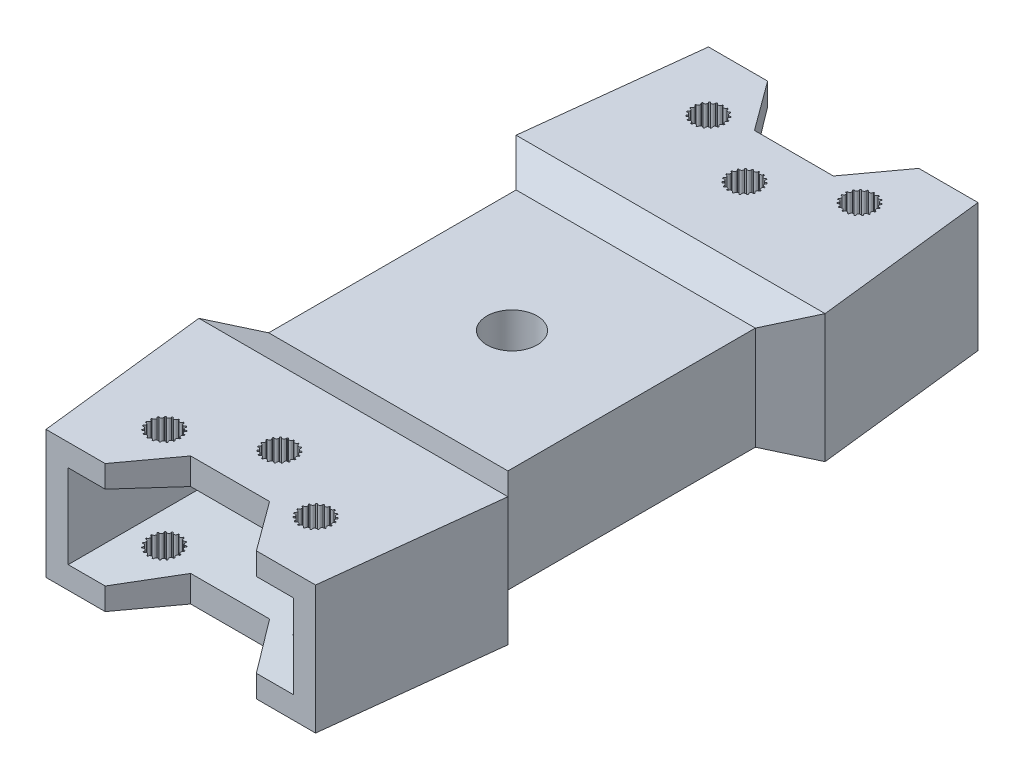
SolidWorks part; units mm, degrees
material "ABS"
ref_plane "Front Plane" through (0, 0, 0) normal (0, 0, 1) x (1, 0, 0)
ref_plane "Top Plane" through (0, 0, 0) normal (0, 1, 0) x (1, 0, 0)
ref_plane "Right Plane" through (0, 0, 0) normal (1, 0, 0) x (0, 0, -1)
sketch "Sketch2" plane through (0, 0, 0) normal (0, 1, 0) x (1, 0, 0)
  line L0 (0, 0) -> (0, 3) construction
  line L1 (0, 175) -> (168.3275, 175) construction
  line L2 (168.3275, 175) -> (-205.8504, 175) construction
  line L3 (-15, 350) -> (-35, 175)
  line L4 (-35, 175) -> (-15, 0)
  line L5 (15, 350) -> (35, 175)
  line L6 (35, 175) -> (15, 0)
  line L7 (0, 335) -> (0, 350) construction
  line L8 (31.3255, 207.1517) -> (24.2545, 200.0806)
  line L9 (24.2545, 200.0806) -> (24.2545, 149.9194)
  line L10 (31.3255, 142.8483) -> (24.2545, 149.9194)
  line L11 (-31.3255, 142.8483) -> (-24.2545, 149.9194)
  line L12 (-24.2545, 200.0806) -> (-24.2545, 149.9194)
  line L13 (-31.3255, 207.1517) -> (-24.2545, 200.0806)
  circle A0 centre (0, 350) radius 3
  circle A1 centre (0, 0) radius 3
  arc A2 (15, 350) -> (-15, 350) centre (0, 350) ccw
  arc A3 (-15, 0) -> (15, 0) centre (0, 0) ccw
  circle A4 centre (0, 175) radius 5.1
  point P21 (24.2545, 175)
  dimension "D2" = 6
  dimension "D3" = 6
  dimension "D4" = 30
  dimension "D5" = 30
  dimension "D7" = 10.2
  dimension "D1" = 350
  dimension "D6" = 35
  dimension "D8" = 32.1517
  dimension "D9" = 10
extrude "Boss-Extrude1" add sketch "Sketch2" along normal blind 26 contours L4 A3 L6 L10 L9 L8 L5 A2 L3 L13 L12 L11 A4 A0 A1 region at (0, 0, -361.1487)
sketch "Sketch3" plane through (0, 0, 0) normal (1, 0, 0) x (0, 0, -1)
  line L0 (-15, 13) -> (370.2756, 13) construction
  line L1 (-15, 26) -> (-15, 0) construction
  line L3 (177.6378, 13) -> (177.6378, -89.1144) construction
  line L5 (-50, 21) -> (20, 21)
  line L6 (-50, 21) -> (-50, 5)
  line L7 (-50, 5) -> (20, 5)
  line L8 (20, 21) -> (20, 5)
  line L9 (-50, 21) -> (20, 5) construction
  line L10 (-50, 5) -> (20, 21) construction
  dimension "D1" = 16
  dimension "D2" = 35
extrude "Cut-Extrude1" cut sketch "Sketch3" against normal mid plane 55
sketch "Sketch4" plane through (0, 26, 0) normal (0, 1, 0) x (1, 0, 0)
  circle A0 centre (0, 175) radius 5
sketch "Sketch5" plane through (24.2545, 0, 0) normal (1, 0, 0) x (0, 0, -1)
  line L0 (149.9194, 13) -> (220.8721, 13) construction
  line L1 (149.9194, 26) -> (149.9194, 0) construction
  line L2 (175, 0) -> (175, 36.8039) construction
  line L3 (200.0806, 0) -> (149.9194, 0) construction
  line L4 (142.8483, 26) -> (149.9194, 23.4568)
  line L5 (149.9194, 23.4568) -> (200.0806, 23.4568)
  line L6 (142.8483, 26) -> (207.1517, 26)
  line L7 (207.1517, 26) -> (200.0806, 23.4568)
  line L8 (207.1517, 0) -> (200.0806, 2.5432)
  line L9 (149.9194, 2.5432) -> (200.0806, 2.5432)
  line L10 (142.8483, 0) -> (149.9194, 2.5432)
  line L11 (142.8483, 0) -> (207.1517, 0)
  point P14 (175, 23.4568)
  point P15 (175, 26)
extrude "Cut-Extrude2" cut sketch "Sketch5" against normal mid plane 126
ref_plane "Plane1" through (0, 0, -175) normal (0, 0, 1) x (1, 0, 0)
mirror "Mirror3" about plane through (0, 0, -175) normal (0, 0, 1) of "Cut-Extrude1"
sketch "Sketch9" plane through (0, 23.4568, 0) normal (0, 1, 0) x (1, 0, 0)
  line L0 (-27.3255, 107.8483) -> (-15.3255, 107.8483)
  line L1 (-31.3255, 142.8483) -> (-15, 0) construction
  line L2 (-15.3255, 107.8483) -> (-8, 117.8483)
  line L3 (-8, 117.8483) -> (8, 117.8483)
  line L4 (0, 175) -> (0, 30.7184) construction
  line L5 (-27.3255, 107.8483) -> (-31.0297, 97.9185)
  line L6 (-31.0297, 97.9185) -> (-17.7384, -19.4473)
  line L7 (-17.7384, -19.4473) -> (15.9415, -24.7304)
  line L8 (15.9415, -24.7304) -> (32.6609, 107.8483)
  line L9 (32.6609, 107.8483) -> (27.3255, 107.8483)
  line L10 (31.3255, 142.8483) -> (15, 0) construction
  line L11 (15.3255, 107.8483) -> (8, 117.8483)
  line L12 (27.3255, 107.8483) -> (15.3255, 107.8483)
  line L13 (-31.3255, 142.8483) -> (31.3255, 142.8483) construction
  line L14 (-15.3255, 107.8483) -> (-15.3255, 124.8534) construction
  line L23 (-31.3255, 142.8483) -> (44.7301, 142.8483) construction
  circle A0 centre (0, 127.8483) radius 2
  circle A1 centre (-15.3255, 119.8483) radius 2
  circle A2 centre (15.3255, 119.8483) radius 2
  point P18 (0, 117.8483)
  point P40 (0.5017, 119.3533)
  dimension "D4" = 4
  dimension "D6" = 4
  dimension "D1" = 25
  dimension "D2" = 16
  dimension "D3" = 12
  dimension "D5" = 10
  dimension "D7" = 12
  dimension "D8" = 12
  dimension "D9" = 10
extrude "Cut-Extrude3" cut sketch "Sketch9" along normal blind 68 and the other way blind 68
sketch "Sketch10" plane through (0, 0, -107.8483) normal (0, 0, 1) x (1, 0, 0)
  line L0 (-22.8255, 4.5) -> (22.8255, 4.5)
  line L5 (22.8255, 4.5) -> (22.8255, 21.5)
  line L6 (-22.8255, 21.5) -> (22.8255, 21.5)
  line L7 (-22.8255, 4.5) -> (-22.8255, 21.5)
  line L8 (-27.3255, 0) -> (-27.3255, 26) construction
  line L10 (27.3255, 0) -> (27.3255, 26) construction
  line L11 (8, 26) -> (-8, 26) construction
  line L12 (8, 0) -> (-8, 0) construction
  line M9 (-15.3255, 0) -> (-15.3255, 26)
  dimension "D1" = 4.5
  dimension "D2" = 4.5
  dimension "D3" = 4.5
  dimension "D4" = 4.5
extrude "Cut-Extrude4" cut sketch "Sketch10" against normal blind 28 draft 5 contours L6 L0 L5 M9 | L7 L0 L6 M9 region at (-19.0755, 13, -107.8483) region at (3.75, 13, -107.8483)
mirror "Mirror5" about plane through (0, 0, -175) normal (0, 0, 1) of "Cut-Extrude4", "Cut-Extrude3"
sketch "Sketch11" plane through (0, 0, 0) normal (0, -1, 0) x (1, 0, 0)
  line L0 (0, -117.8483) -> (0, -161.1562) construction
  line L1 (8, -117.8483) -> (-8, -117.8483) construction
  line L2 (-15.3255, -119.8483) -> (-22.194, -119.8483) construction
  circle A0 centre (-15.3255, -119.8483) radius 3.25
  circle A1 centre (-18.5755, -119.8483) radius 0.4
  circle A2 centre (-18.3994, -118.793) radius 0.4
  circle A3 centre (-17.8902, -117.8521) radius 0.4
  circle A4 centre (-17.1031, -117.1275) radius 0.4
  circle A5 centre (-16.1233, -116.6977) radius 0.4
  circle A6 centre (-15.0571, -116.6094) radius 0.4
  circle A7 centre (-14.02, -116.872) radius 0.4
  circle A8 centre (-13.1244, -117.4572) radius 0.4
  circle A9 centre (-12.4672, -118.3015) radius 0.4
  circle A10 centre (-12.1198, -119.3134) radius 0.4
  circle A11 centre (-12.1198, -120.3832) radius 0.4
  circle A12 centre (-12.4672, -121.3951) radius 0.4
  circle A13 centre (-13.1244, -122.2394) radius 0.4
  circle A14 centre (-14.02, -122.8246) radius 0.4
  circle A15 centre (-15.0571, -123.0872) radius 0.4
  circle A16 centre (-16.1233, -122.9988) radius 0.4
  circle A17 centre (-17.1031, -122.5691) radius 0.4
  circle A18 centre (-17.8902, -121.8445) radius 0.4
  circle A19 centre (-18.3994, -120.9036) radius 0.4
  circle A20 centre (0, -127.8483) radius 3.25
  circle A21 centre (15.3255, -119.8483) radius 3.25
  circle A22 centre (-3.25, -127.8483) radius 0.4
  circle A23 centre (12.0755, -119.8483) radius 0.4
  circle A24 centre (-3.0739, -126.793) radius 0.4
  circle A25 centre (-2.5647, -125.8521) radius 0.4
  circle A26 centre (-1.7776, -125.1275) radius 0.4
  circle A27 centre (-0.7978, -124.6977) radius 0.4
  circle A28 centre (0.2684, -124.6094) radius 0.4
  circle A29 centre (1.3055, -124.872) radius 0.4
  circle A30 centre (2.2012, -125.4572) radius 0.4
  circle A31 centre (2.8583, -126.3015) radius 0.4
  circle A32 centre (3.2057, -127.3134) radius 0.4
  circle A33 centre (3.2057, -128.3832) radius 0.4
  circle A34 centre (2.8583, -129.3951) radius 0.4
  circle A35 centre (2.2012, -130.2394) radius 0.4
  circle A36 centre (1.3055, -130.8246) radius 0.4
  circle A37 centre (0.2684, -131.0872) radius 0.4
  circle A38 centre (-0.7978, -130.9988) radius 0.4
  circle A39 centre (-1.7776, -130.5691) radius 0.4
  circle A40 centre (-2.5647, -129.8445) radius 0.4
  circle A41 centre (-3.0739, -128.9036) radius 0.4
  circle A42 centre (12.2516, -118.793) radius 0.4
  circle A43 centre (12.7608, -117.8521) radius 0.4
  circle A44 centre (13.5479, -117.1275) radius 0.4
  circle A45 centre (14.5277, -116.6977) radius 0.4
  circle A46 centre (15.5939, -116.6094) radius 0.4
  circle A47 centre (16.631, -116.872) radius 0.4
  circle A48 centre (17.5267, -117.4572) radius 0.4
  circle A49 centre (18.1838, -118.3015) radius 0.4
  circle A50 centre (18.5312, -119.3134) radius 0.4
  circle A51 centre (18.5312, -120.3832) radius 0.4
  circle A52 centre (18.1838, -121.3951) radius 0.4
  circle A53 centre (17.5267, -122.2394) radius 0.4
  circle A54 centre (16.631, -122.8246) radius 0.4
  circle A55 centre (15.5939, -123.0872) radius 0.4
  circle A56 centre (14.5277, -122.9988) radius 0.4
  circle A57 centre (13.5479, -122.5691) radius 0.4
  circle A58 centre (12.7608, -121.8445) radius 0.4
  circle A59 centre (12.2516, -120.9036) radius 0.4
  circle M2 centre (15.3255, -119.8483) radius 2
  circle M3 centre (-15.3255, -119.8483) radius 2
  circle M4 centre (0, -127.8483) radius 2
  dimension "D1" = 6.5
  dimension "D2" = 0.8
  dimension "D4" = 6.5
  dimension "D5" = 6.5
  dimension "D6" = 0.8
  dimension "D7" = 0.8
  dimension "D3" = 19
  dimension "D8" = 19
  dimension "D9" = 19
extrude "Cut-Extrude5" cut sketch "Sketch11" against normal blind 54 contours A19 A0 A18 A17 A16 A15 A14 A13 A12 A11 A10 A9 A8 A7 A6 A5 A4 A3 A2 A1 M3 | A41 A20 A40 A39 A38 A37 A36 A35 A34 A33 A32 A31 A30 A29 A28 A27 A26 A25 A24 A22 M4 | A59 A21 A58 A57 A56 A55 A54 A53 A52 A51 A50 A49 A48 A47 A46 A45 A44 A43 A42 A23 M2 region at (-12.1679, 0, -119.9149) region at (3.1576, 0, -127.9149) region at (18.4831, 0, -119.9149)
mirror "Mirror6" about plane through (0, 0, -175) normal (0, 0, 1) of "Cut-Extrude5"
sketch "Sketch12" plane through (0, 2.5432, 0) normal (0, -1, 0) x (1, 0, 0)
  circle A0 centre (0, -175) radius 8.5
  dimension "D1" = 17
extrude "Cut-Extrude6" cut sketch "Sketch12" against normal blind 10
